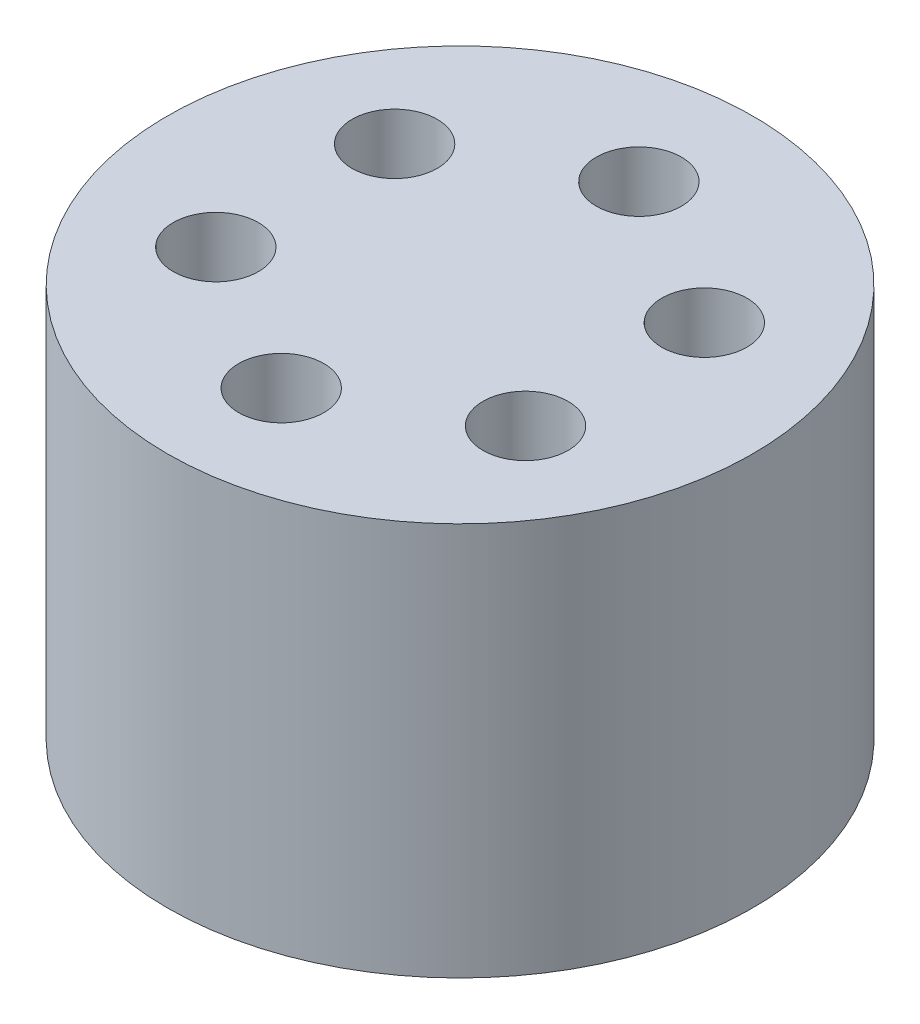
SolidWorks part; units mm, degrees
ref_plane "Front Plane" through (0, 0, 0) normal (0, 0, 1) x (1, 0, 0)
ref_plane "Top Plane" through (0, 0, 0) normal (0, 1, 0) x (1, 0, 0)
ref_plane "Right Plane" through (0, 0, 0) normal (1, 0, 0) x (0, 0, -1)
sketch "Sketch1" plane through (0, 0, 0) normal (0, 1, 0) x (1, 0, 0)
  circle A0 centre (0, 0) radius 18.9
extrude "Boss-Extrude1" add sketch "Sketch1" along normal blind 25.4
sketch "Sketch2" plane through (0, 25.4, 0) normal (0, 1, 0) x (1, 0, 0)
  line L1 (0, 11.547) -> (-10, 5.7735)
  line L2 (-10, 5.7735) -> (-10, -5.7735)
  line L3 (-10, -5.7735) -> (0, -11.547)
  line L4 (0, -11.547) -> (10, -5.7735)
  line L5 (10, -5.7735) -> (10, 5.7735)
  line L6 (10, 5.7735) -> (0, 11.547)
  circle A0 centre (0, 0) radius 10 construction
  circle A1 centre (0, 11.547) radius 2.75
  circle A2 centre (10, 5.7735) radius 2.75
  circle A3 centre (10, -5.7735) radius 2.75
  circle A4 centre (0, -11.547) radius 2.75
  circle A5 centre (-10, -5.7735) radius 2.75
  circle A6 centre (-10, 5.7735) radius 2.75
extrude "Cut-Extrude1" cut sketch "Sketch2" against normal blind 25.4 contours L1 A6 L2 | L2 A6 L1 | L6 A1 L1 | L1 A1 L6 | L5 A2 L6 | L6 A2 L5 | L4 A3 L5 | L5 A3 L4 | L3 A4 L4 | L4 A4 L3 | L2 A5 L3 | L3 A5 L2 region at (0, 25.4, -10.0309) region at (0, 25.4, -12.3051) region at (-8.687, 25.4, -5.0154) region at (-10.6565, 25.4, -6.1525) region at (10.6565, 25.4, -6.1525) region at (8.687, 25.4, -5.0154) region at (-8.687, 25.4, 5.0154) region at (-10.6565, 25.4, 6.1525) region at (10.6565, 25.4, 6.1525) region at (8.687, 25.4, 5.0154) region at (0, 25.4, 10.0309) region at (0, 25.4, 12.3051)
